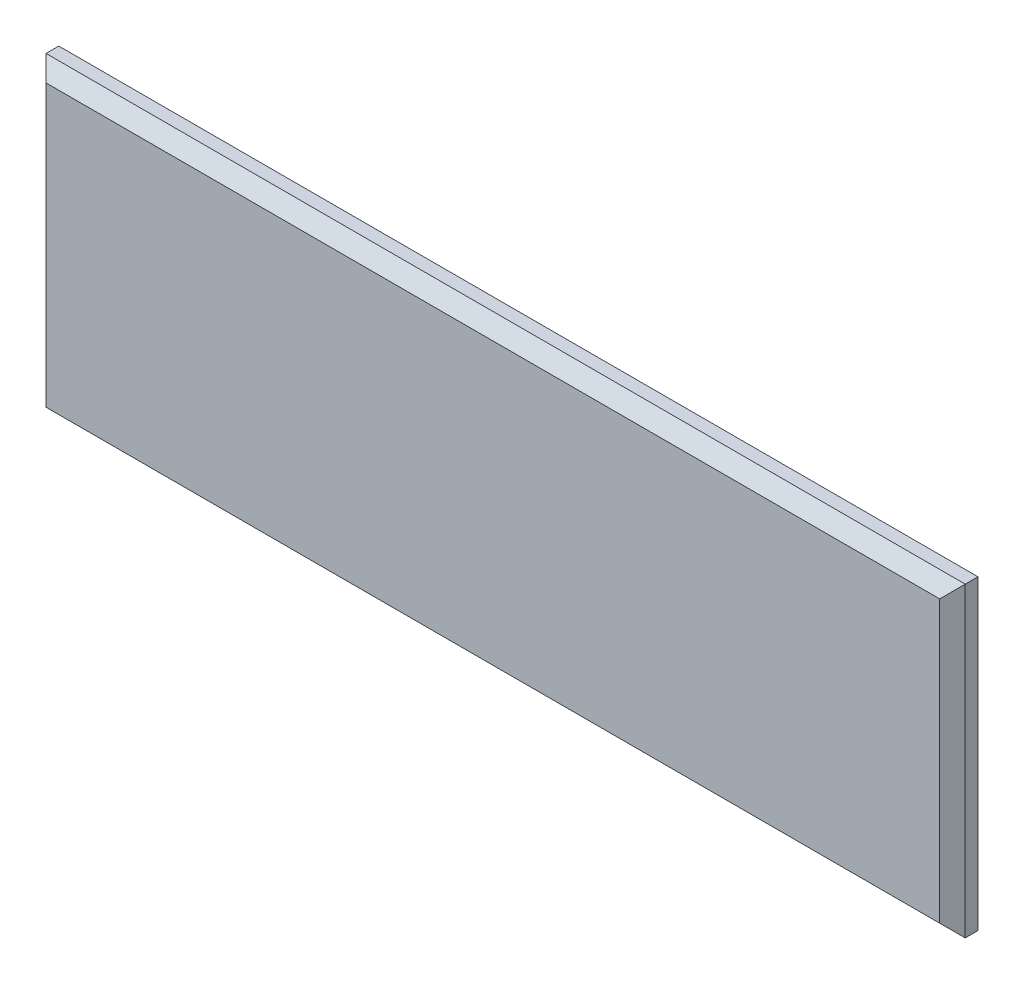
SolidWorks part; units mm, degrees
ref_plane "Top Plane" through (0, 0, 0) normal (0, 0, 1) x (1, 0, 0)
ref_plane "Front Plane" through (0, 0, 0) normal (0, 1, 0) x (1, 0, 0)
ref_plane "Right Plane" through (0, 0, 0) normal (1, 0, 0) x (0, 0, -1)
sketch "Profile Sketch" plane through (0, 0, 0) normal (0, 0, 1) x (1, 0, 0)
  line L1 (-457.2, -152.4) -> (457.2, -152.4)
  line L2 (-457.2, -152.4) -> (-457.2, 152.4)
  line L3 (-457.2, 152.4) -> (457.2, 152.4)
  line L4 (457.2, -152.4) -> (457.2, 152.4)
  line L5 (-457.2, -152.4) -> (457.2, 152.4) construction
  line L6 (-457.2, 152.4) -> (457.2, -152.4) construction
  point P0 (0, 0)
  dimension "D1" = 914.4
  dimension "D2" = 304.8
extrude "Profile Extrude" add sketch "Profile Sketch" along normal blind 25.4
chamfer "Edge Chamfer" distance 12.7 angle 45 4 edges at (0, -152.4, 25.4) (-457.2, 0, 25.4) (0, 152.4, 25.4) (457.2, 0, 25.4)
sketch "Centering Sketch" plane through (0, 0, 25.4) normal (0, 0, 1) x (1, 0, 0)
  line L0 (-457.2, 0) -> (457.2, 0) construction
  line L4 (457.2, -152.4) -> (457.2, 152.4)
  line L5 (-457.2, -152.4) -> (457.2, -152.4)
  line L6 (-457.2, 152.4) -> (-457.2, -152.4)
  line L7 (457.2, 152.4) -> (-457.2, 152.4)
  line L8 (457.2, -152.4) -> (457.2, 152.4) construction
  line L10 (-457.2, 152.4) -> (-457.2, -152.4) construction
  point P6 (0, 0)
  dimension "D1" = 0
